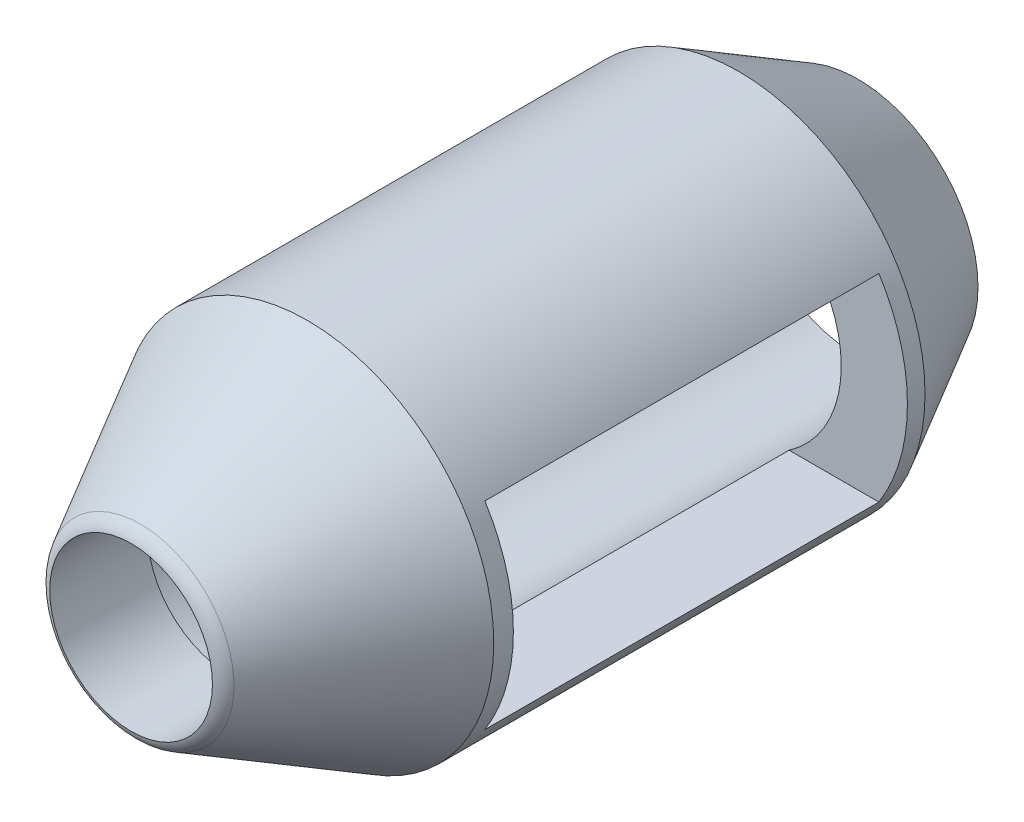
SolidWorks part; units mm, degrees
ref_plane "Piano frontale" through (0, 0, 0) normal (0, 0, 1) x (1, 0, 0)
ref_plane "Piano superiore" through (0, 0, 0) normal (0, 1, 0) x (1, 0, 0)
ref_plane "Piano destro" through (0, 0, 0) normal (1, 0, 0) x (0, 0, -1)
sketch "Schizzo1" plane through (0, 0, 0) normal (0, 0, 1) x (1, 0, 0)
  circle A0 centre (0, 0) radius 4.15
  circle A1 centre (0, 0) radius 9.5
  dimension "D1" = 8.3
  dimension "D2" = 19
extrude "Estrusione-Estrusione1" add sketch "Schizzo1" along normal blind 40
ref_plane "Piano1" through (9.5, 0, 0) normal (1, 0, 0) x (0, 0, -1)
sketch "Schizzo2" plane through (9.5, 0, 0) normal (1, 0, 0) x (0, 0, -1)
  line L0 (-40, 0) -> (49960, 0) construction
  line L1 (-40, 9.5) -> (-40, -9.5) construction
  line L3 (-30, 5.05) -> (-9.9, 5.05)
  line L4 (-30, 5.05) -> (-30, -5.05)
  line L5 (-30, -5.05) -> (-9.9, -5.05)
  line L6 (-9.9, 5.05) -> (-9.9, -5.05)
  line L7 (-30, 5.05) -> (-9.9, -5.05) construction
  line L8 (-30, -5.05) -> (-9.9, 5.05) construction
  point P4 (-40, 0)
  point P5 (-19.95, 0)
  dimension "D1" = 20.1
  dimension "D2" = 10.1
  dimension "D3" = 10
extrude "Taglio-Estrusione1" cut sketch "Schizzo2" against normal through all
chamfer "Smusso1" distance 9 distance2 5 2 edges at (9.5, 0, 0) (9.5, 0, 40) first distance on face at (-8.7733, 0, 19.95)
fillet "Raccordo1" radius 1 1 edges at (4.5, 0, 40)
sketch "Schizzo3" plane through (0, 0, 0) normal (0, 0, -1) x (-1, 0, 0)
  circle A0 centre (0, 0) radius 6.125
  dimension "D1" = 12.25
extrude "Taglio-Estrusione2" cut sketch "Schizzo3" against normal blind 35
